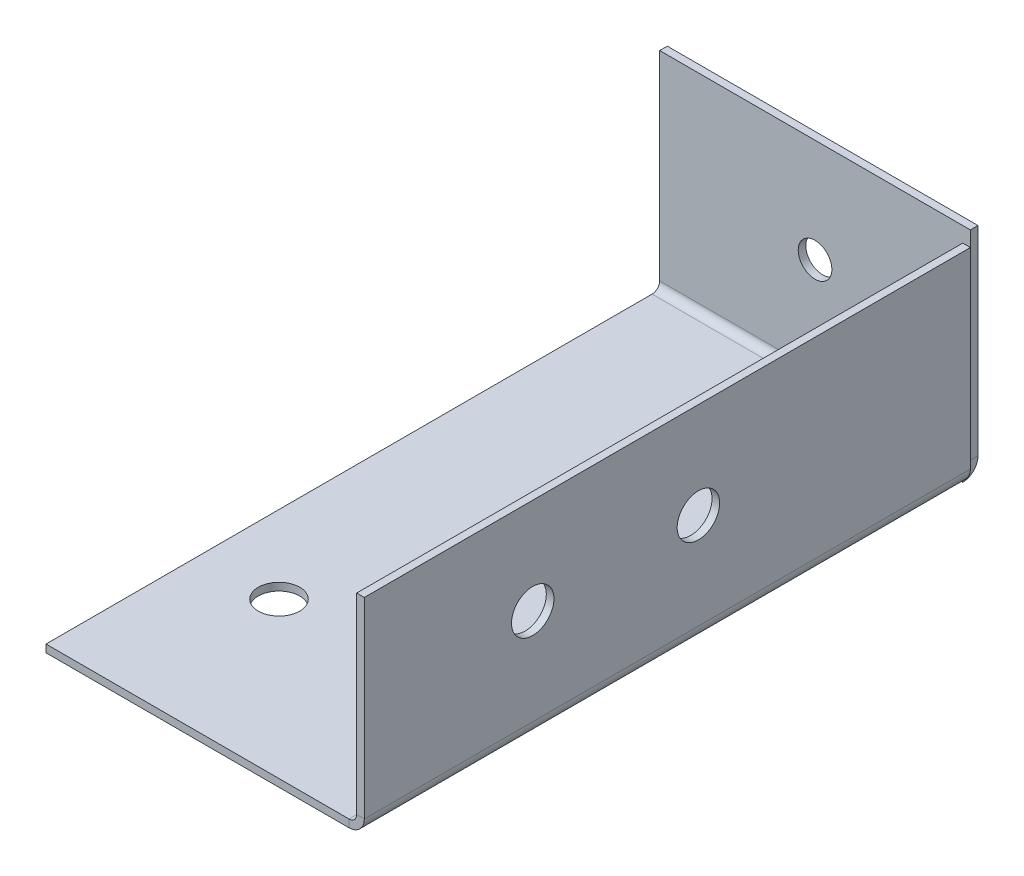
SolidWorks part; units mm, degrees
note: The reader was unsure of these and kept them because the rebuilt part matched: flange length of "Edge-Flange1", "Edge-Flange6".
ref_plane "Front Plane" through (0, 0, 0) normal (0, 0, 1) x (1, 0, 0)
ref_plane "Top Plane" through (0, 0, 0) normal (0, 1, 0) x (1, 0, 0)
ref_plane "Right Plane" through (0, 0, 0) normal (1, 0, 0) x (0, 0, -1)
sketch "Sketch1" plane through (0, 0, 0) normal (0, 1, 0) x (1, 0, 0)
  line L1 (-15, -30) -> (15, -30)
  line L2 (-15, -30) -> (-15, 30)
  line L3 (-15, 30) -> (15, 30)
  line L4 (15, -30) -> (15, 30)
  line L5 (-15, -30) -> (15, 30) construction
  line L6 (-15, 30) -> (15, -30) construction
  circle A0 centre (7.5, -15) radius 2
  circle A1 centre (0, 15) radius 2
  circle A2 centre (-7.5, -15) radius 2
  point P0 (0, 0)
  dimension "D3" = 4
  dimension "D4" = 4
  dimension "D5" = 4
  dimension "D7" = 7.5
  dimension "D1" = 60
  dimension "D2" = 30
  dimension "D6" = 15
  dimension "D8" = 15
  dimension "D9" = 15
  dimension "D10" = 7.5
  dimension "D11" = 15
base flange "Base-Flange1" sketch "Sketch1" thickness 0.7366 reverse thickness direction no parameters "D1"=0.7366
edge flange "Edge-Flange1" sketch "Sketch8" flange angle 90 flange length 20.7366 flange position material inside bend radius 0.7366 thickness 0.7366 relief rectangular parameters "D6"=10
sketch "Sketch8" plane through (0, 0, -30) normal (0, 0, -1) x (-1, 0, 0)
  line L0 (-15, 0) -> (15, 0) construction
  line L1 (-15, 0) -> (15, 0)
  line L2 (-15, 0) -> (-15, 20)
  line L3 (15, 20) -> (-15, 20)
  line L4 (15, 20) -> (15, 0)
  circle A1 centre (0, 10) radius 1.625
  dimension "D2" = 3.25
  dimension "D1" = 20
  dimension "D3" = 10
bend "EdgeBend1" bend radius 0.7366 bend angle 90 parameters "D5"=1
edge flange "Edge-Flange6" sketch "Sketch23" flange angle 90 flange length 20 flange position material outside bend radius 0.7366 thickness 0.7366 relief none parameters "D6"=10
sketch "Sketch23" plane through (15, 0, 0) normal (1, 0, 0) x (0, 0, -1)
  line L0 (-30, 0) -> (28.5268, 0) construction
  line L1 (-30, 0) -> (28.5268, 0)
  line L2 (-30, 0) -> (-30, 19.2634)
  line L3 (-30, 19.2634) -> (28.5268, 19.2634)
  line L4 (28.5268, 19.2634) -> (28.5268, 0)
bend "EdgeBend6" bend radius 0.7366 bend angle 90 parameters "D5"=2
extrude "Cut-Extrude1" cut sketch "Sketch24" against normal through all normal cut yes
sketch "Sketch24" plane through (385, -11.7404, -44.8739) normal (1, 0, 0) x (0, 0, -1)
  circle A3 centre (-42.6105, 21.7404) radius 2.05
  circle A6 centre (-58.6105, 21.7404) radius 2.05
  circle A9 centre (22.8627, 21.7404) radius 2.05
  circle A12 centre (38.8627, 21.7404) radius 2.05
sketch "Bend-Lines1" [suppressed] plane through (0, 0, 0) normal (0, 1, 0) x (1, 0, 0)
sketch "Bounding-Box1" [suppressed] plane through (0, 0, 0) normal (0, 1, 0) x (1, 0, 0)
sketch "Sketch25" [suppressed] plane through (0, 0, 0) normal (0, 1, 0) x (1, 0, 0)
  line L1 (15.3312, 26.5478) -> (14.9312, 26.5478)
  line L2 (15.3312, -30) -> (15.3312, 28.5268)
  line L3 (15.3312, 22.4435) -> (15.3312, 26.5478)
  line L4 (14.9312, -30) -> (14.9312, 28.5268)
  line L5 (14.9312, 22.4435) -> (14.9312, 26.5478)
  line L6 (15.3312, 22.4435) -> (14.9312, 22.4435)
  line L7 (15.3312, 12.4435) -> (14.9312, 12.4435)
  line L8 (15.3312, 12.4435) -> (15.3312, 16.5478)
  line L9 (15.3312, 16.5478) -> (14.9312, 16.5478)
  line L10 (14.9312, 12.4435) -> (14.9312, 16.5478)
  line L11 (15.3312, 2.4435) -> (14.9312, 2.4435)
  line L12 (15.3312, 2.4435) -> (15.3312, 6.5478)
  line L13 (15.3312, 6.5478) -> (14.9312, 6.5478)
  line L14 (14.9312, 2.4435) -> (14.9312, 6.5478)
  line L15 (15.3312, -7.5565) -> (14.9312, -7.5565)
  line L16 (15.3312, -7.5565) -> (15.3312, -3.4522)
  line L17 (15.3312, -3.4522) -> (14.9312, -3.4522)
  line L18 (14.9312, -7.5565) -> (14.9312, -3.4522)
  line L19 (15.3312, -17.5565) -> (14.9312, -17.5565)
  line L20 (15.3312, -17.5565) -> (15.3312, -13.4522)
  line L21 (15.3312, -13.4522) -> (14.9312, -13.4522)
  line L22 (14.9312, -17.5565) -> (14.9312, -13.4522)
  line L23 (15.3312, -27.5565) -> (14.9312, -27.5565)
  line L24 (15.3312, -27.5565) -> (15.3312, -23.4522)
  line L25 (15.3312, -23.4522) -> (14.9312, -23.4522)
  line L26 (14.9312, -27.5565) -> (14.9312, -23.4522)
  line L27 (13.3599, 29.5946) -> (13.3599, 29.1946)
  line L28 (15, 29.5946) -> (-15, 29.5946)
  line L29 (13.3599, 29.5946) -> (11.2425, 29.5946)
  line L30 (15, 29.1946) -> (-15, 29.1946)
  line L31 (13.3599, 29.1946) -> (11.2425, 29.1946)
  line L32 (11.2425, 29.5946) -> (11.2425, 29.1946)
  line L33 (5.3599, 29.1946) -> (3.2425, 29.1946)
  line L34 (5.3599, 29.5946) -> (3.2425, 29.5946)
  line L35 (5.3599, 29.5946) -> (5.3599, 29.1946)
  line L36 (3.2425, 29.5946) -> (3.2425, 29.1946)
  line L37 (-2.6401, 29.1946) -> (-4.7575, 29.1946)
  line L38 (-2.6401, 29.5946) -> (-4.7575, 29.5946)
  line L39 (-2.6401, 29.5946) -> (-2.6401, 29.1946)
  line L40 (-4.7575, 29.5946) -> (-4.7575, 29.1946)
  line L41 (-10.6401, 29.1946) -> (-12.7575, 29.1946)
  line L42 (-10.6401, 29.5946) -> (-12.7575, 29.5946)
  line L43 (-10.6401, 29.5946) -> (-10.6401, 29.1946)
  line L44 (-12.7575, 29.5946) -> (-12.7575, 29.1946)
  dimension "D1" = 0.2
  dimension "D2" = 0.2
  dimension "D4" = 0.2
  dimension "D5" = 0.2
  dimension "D3" = 6
  dimension "D6" = 4
extrude "Cut-Extrude2" [suppressed] cut sketch "Sketch25" against normal blind 10
sheet metal parameters "Sheet-Metal1" thickness 0.7366 parameters "D1"=0.7366
flat pattern "Flat-Pattern1" [suppressed]
sketch "Bend-Lines2" plane through (0, 0, 0) normal (0, 1, 0) x (1, 0, 0)
sketch "Bounding-Box2" [suppressed] plane through (0, 0, 0) normal (0, 1, 0) x (1, 0, 0)
sheet metal parameters "Sheet-Metal2" thickness 0.7366 parameters "D1"=0.7366
flat pattern "Flat-Pattern1" [suppressed]
sketch "Bend-Lines2" plane through (0, 0, 0) normal (0, 1, 0) x (1, 0, 0)
sketch "Bounding-Box2" [suppressed] plane through (0, 0, 0) normal (0, 1, 0) x (1, 0, 0)
bend of the flat pattern "Flatten-<EdgeBend1>1"
sheet metal parameters "Sheet-Metal7" thickness 0.7366 parameters "D1"=0.7366
flat pattern "Flat-Pattern1" [suppressed]
sketch "Bend-Lines2" plane through (0, 0, 0) normal (0, 1, 0) x (1, 0, 0)
sketch "Bounding-Box2" [suppressed] plane through (0, 0, 0) normal (0, 1, 0) x (1, 0, 0)
bend of the flat pattern "Flatten-<EdgeBend1>1"
bend of the flat pattern "Flatten-<EdgeBend6>1"
sheet metal parameters "Sheet-Metal8" thickness 0.7366 parameters "D1"=0.7366
flat pattern "Flat-Pattern1"
sketch "Bend-Lines2" plane through (0, 0, 0) normal (0, 1, 0) x (1, 0, 0)
  line L0 (15.1312, -30) -> (15.1312, 28.5268) construction
  line L1 (15, 29.3946) -> (-15, 29.3946) construction
  line L2 (15.1312, -30) -> (15.1312, 28.5268) construction
  line L3 (15, 29.3946) -> (-15, 29.3946) construction
sketch3d "Bounding-Box2" [suppressed]
  line L0 (-15, -30, 0) -> (-15, 49.5258, 0) construction
  line L1 (34.5258, -30, 0) -> (34.5258, 49.5258, 0) construction
  line L2 (-15, -30, 0) -> (34.5258, -30, 0) construction
  line L3 (-15, 49.5258, 0) -> (34.5258, 49.5258, 0) construction
bend of the flat pattern "Flatten-<EdgeBend1>1"
bend of the flat pattern "Flatten-<EdgeBend6>1"
